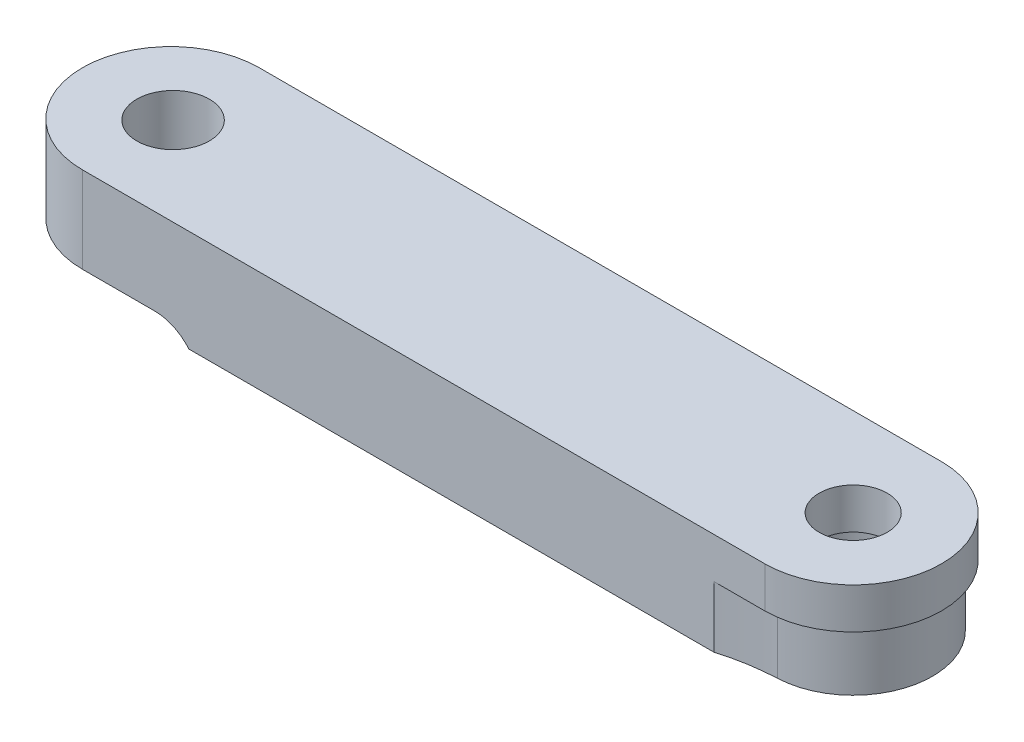
SolidWorks part; units mm, degrees
ref_plane "Front Plane" through (0, 0, 0) normal (0, 0, 1) x (1, 0, 0)
ref_plane "Top Plane" through (0, 0, 0) normal (0, 1, 0) x (1, 0, 0)
ref_plane "Right Plane" through (0, 0, 0) normal (1, 0, 0) x (0, 0, -1)
sketch "Sketch1" plane through (0, 0, 0) normal (0, 1, 0) x (1, 0, 0)
  circle A0 centre (0, 0) radius 3.5
  circle A1 centre (0, 0) radius 2.25
  dimension "D1" = 7
  dimension "D2" = 4.5
extrude "Boss-Extrude1" add sketch "Sketch1" along normal blind 2.7
sketch "Sketch2" plane through (0, 2.7, 0) normal (0, 1, 0) x (1, 0, 0)
  line L0 (0, -3.5) -> (0, 3.5) construction
  line L1 (-56.7, 0) -> (-3.5, 0) construction
  line L2 (0, 3.9) -> (-30.1, 3.9)
  line L3 (0, -3.9) -> (-30.1, -3.9)
  circle A0 centre (0, 0) radius 3.5 construction
  arc A1 (-30.1, 3.9) -> (-30.1, -3.9) centre (-30.1, 0) ccw
  circle A3 centre (-30, 0) radius 1.6
  circle A11 centre (0, 0) radius 1.5
  arc A12 (0, 3.9) -> (0, -3.9) centre (0, 0) cw
  point P9 (-34, 0)
  dimension "D3" = 30
  dimension "D4" = 3.2
  dimension "D5" = 4
  dimension "D8" = 3
  dimension "D9" = 3.9
  dimension "D1" = 7.8
  dimension "D2" = 7.8
extrude "Boss-Extrude2" add sketch "Sketch2" along normal blind 1.8
sketch "Sketch3" plane through (0, 0, 0) normal (0, 0, 1) x (1, 0, 0)
  line L0 (-3.5, 0) -> (-25.4, 0)
  line L1 (-31.6, 2.7) -> (-28.4, 2.7) construction
  line L2 (-31.6, 2.7) -> (-28.4, 2.7)
  line L3 (-25.4, 0) -> (-25.4, 2.7)
  line L4 (-30.1, 2.7) -> (0, 2.7) construction
  line L9 (-3.5, 0) -> (-2.25, 0)
  line L10 (-2.25, 0) -> (-2.25, 2.7)
  line L11 (-25.4, 2.7) -> (-2.25, 2.7)
  line L12 (-34, 2.7) -> (-34, 0.7)
  line L13 (-34, 0.7) -> (-25.4, 0.7)
  line L14 (-34, 2.7) -> (-25.4, 2.7)
  dimension "D1" = 3
  dimension "D2" = 2
extrude "Boss-Extrude3" add sketch "Sketch3" along normal mid plane 7.8 contours L11 L3 L0 L9 L10 | L14 L12 L13 L3 L2 region at (-13.825, 1.35, 0) region at (-29.7, 1.7, 0)
fillet "Fillet1" radius 10 2 edges at (-2.25, 1.35, 2.681) (-2.25, 1.35, -2.681)
sketch "Sketch4" plane through (0, 2.7, 0) normal (0, 1, 0) x (1, 0, 0)
  line L0 (-34, -3.9) -> (-30.1, -3.9) construction
  line L1 (-34, -3.9) -> (-34, 0) construction
  line L2 (-34, 3.9) -> (-30.1, 3.9) construction
  line L3 (-34, 0) -> (-34, 3.9) construction
  line L4 (-34, -3.9) -> (-30.1, -3.9)
  line L5 (-34, -3.9) -> (-34, 0)
  line L6 (-34, 3.9) -> (-30.1, 3.9)
  line L7 (-34, 0) -> (-34, 3.9)
  arc A0 (-30.1, 3.9) -> (-30.1, -3.9) centre (-30.1, 0) ccw construction
  arc A1 (-30.1, 3.9) -> (-30.1, -3.9) centre (-30.1, 0) ccw
  circle A2 centre (-30, 0) radius 1.6 construction
  circle A3 centre (-30, 0) radius 1.6
  arc M1 (-34, 0) -> (-30.1, 3.9) centre (-30.1, 0) cw
  line M2 (-30.1, 3.9) -> (-34, 3.9)
  line M3 (-34, 3.9) -> (-34, 0)
extrude "Cut-Extrude1" cut sketch "Sketch4" against normal blind 8 contours M3 M1 M2 | A1 L5 L4 | A3 region at (-33.1289, 2.7, 3.0289) region at (-33.1289, 2.7, -3.0289) region at (-30, 2.7, 0)
fillet "Fillet2" radius 2 1 edges at (-25.4, 0.7, 0)
